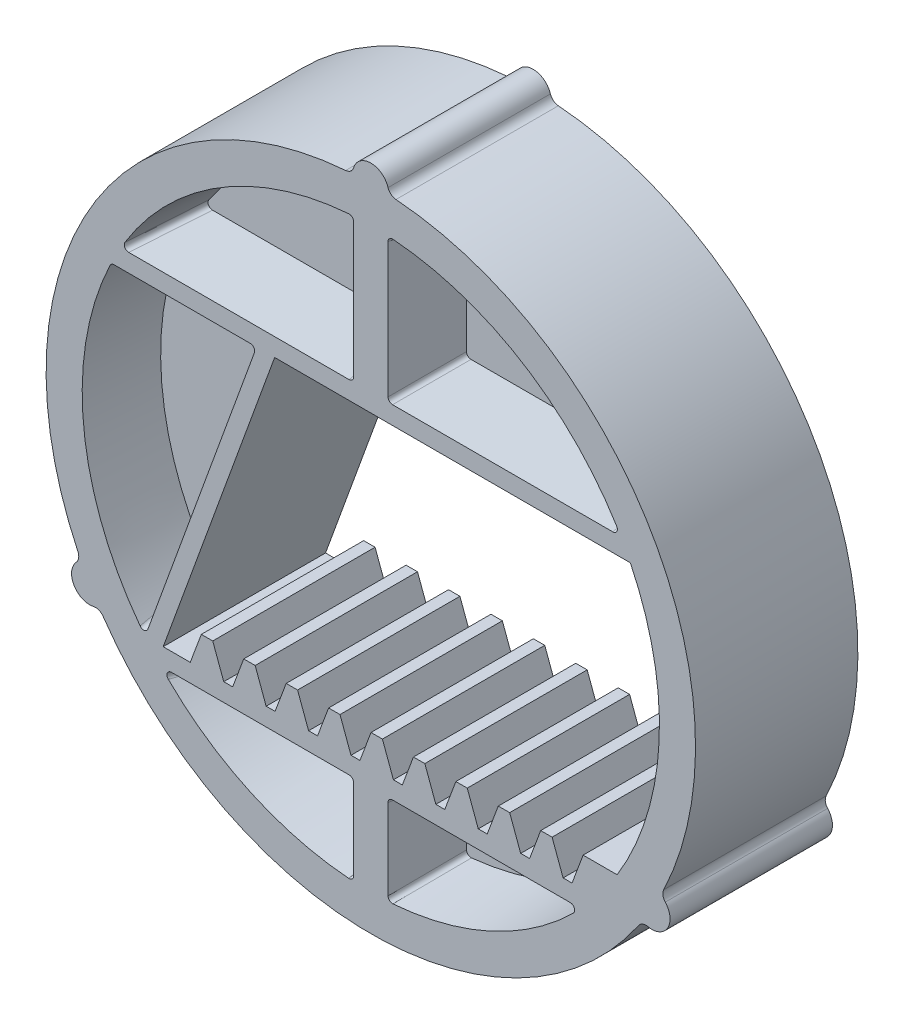
SolidWorks part; units mm, degrees
ref_plane "Plan de face" through (0, 0, 0) normal (0, 0, 1) x (1, 0, 0)
ref_plane "Plan de dessus" through (0, 0, 0) normal (0, 1, 0) x (1, 0, 0)
ref_plane "Plan de droite" through (0, 0, 0) normal (1, 0, 0) x (0, 0, -1)
sketch "Esquisse1" plane through (0, 0, 0) normal (0, 0, 1) x (1, 0, 0)
  line L0 (14.3875, 7) -> (-5.3312, 7)
  line L1 (-5.3312, 7) -> (-11.5097, -9.9753)
  line L2 (-11.5097, -9.9753) -> (-10.0097, -9.9753)
  line L3 (-7.6582, -9.977) -> (-8.1539, -9.977)
  line L4 (-8.1539, -9.977) -> (-8.7634, -8.3253)
  line L5 (-8.7634, -8.3253) -> (-9.3955, -8.3253)
  line L6 (-9.3955, -8.3253) -> (-10.0097, -9.9753)
  line L7 (-5.3067, -9.9787) -> (-5.8023, -9.9787)
  line L8 (-5.8023, -9.9787) -> (-6.4119, -8.327)
  line L9 (-6.4119, -8.327) -> (-7.044, -8.327)
  line L10 (-7.044, -8.327) -> (-7.6582, -9.977)
  line L11 (-2.9552, -9.9805) -> (-3.4508, -9.9805)
  line L12 (-3.4508, -9.9805) -> (-4.0603, -8.3287)
  line L13 (-4.0603, -8.3287) -> (-4.6925, -8.3287)
  line L14 (-4.6925, -8.3287) -> (-5.3067, -9.9787)
  line L15 (-0.6036, -9.9822) -> (-1.0993, -9.9822)
  line L16 (-1.0993, -9.9822) -> (-1.7088, -8.3305)
  line L17 (-1.7088, -8.3305) -> (-2.341, -8.3305)
  line L18 (-2.341, -8.3305) -> (-2.9552, -9.9805)
  line L19 (1.7479, -9.9839) -> (1.2522, -9.9839)
  line L20 (1.2522, -9.9839) -> (0.6427, -8.3322)
  line L21 (0.6427, -8.3322) -> (0.0106, -8.3322)
  line L22 (0.0106, -8.3322) -> (-0.6036, -9.9822)
  line L23 (4.0994, -9.9857) -> (3.6038, -9.9857)
  line L24 (3.6038, -9.9857) -> (2.9942, -8.3339)
  line L25 (2.9942, -8.3339) -> (2.3621, -8.3339)
  line L26 (2.3621, -8.3339) -> (1.7479, -9.9839)
  line L27 (6.451, -9.9874) -> (5.9553, -9.9874)
  line L28 (5.9553, -9.9874) -> (5.3458, -8.3357)
  line L29 (5.3458, -8.3357) -> (4.7136, -8.3357)
  line L30 (4.7136, -8.3357) -> (4.0994, -9.9857)
  line L31 (8.8025, -9.9891) -> (8.3068, -9.9891)
  line L32 (8.3068, -9.9891) -> (7.6973, -8.3374)
  line L33 (7.6973, -8.3374) -> (7.0652, -8.3374)
  line L34 (7.0652, -8.3374) -> (6.451, -9.9874)
  line L35 (11.154, -9.9909) -> (10.6584, -9.9909)
  line L36 (10.6584, -9.9909) -> (10.0488, -8.3391)
  line L37 (10.0488, -8.3391) -> (9.4167, -8.3391)
  line L38 (9.4167, -8.3391) -> (8.8025, -9.9891)
  line L39 (0, -4.95) -> (0, 4.95) construction
  line L41 (13.6539, -8.3409) -> (11.7682, -8.3409)
  line L42 (11.7682, -8.3409) -> (11.154, -9.9909)
  arc A0 (-14.8447, -10.1801) -> (14.8447, -10.1801) centre (0, 0) ccw
  circle A1 centre (0, 0) radius 16
  arc A2 (-16.3226, -8.321) -> (-15.3675, -9.9753) centre (-15.5885, -9) ccw
  arc A3 (-16.3226, -8.321) -> (-16.2386, -7.7658) centre (-16.6897, -7.9815) ccw
  arc A4 (-15.3675, -9.9753) -> (-14.8447, -10.1801) centre (-15.257, -10.4629) cw
  arc A5 (0.9551, 18.2963) -> (-0.9551, 18.2963) centre (0, 18) ccw
  arc A6 (0.9551, 18.2963) -> (1.3939, 17.9459) centre (1.4326, 18.4444) ccw
  arc A7 (-0.9551, 18.2963) -> (-1.3939, 17.9459) centre (-1.4326, 18.4444) cw
  arc A8 (15.3675, -9.9753) -> (14.8447, -10.1801) centre (15.257, -10.4629) ccw
  arc A9 (16.3226, -8.321) -> (16.2386, -7.7658) centre (16.6897, -7.9815) cw
  arc A10 (16.3226, -8.321) -> (15.3675, -9.9753) centre (15.5885, -9) cw
  arc A11 (16.2386, -7.7658) -> (1.3939, 17.9459) centre (0, 0) ccw
  arc A12 (-1.3939, 17.9459) -> (-16.2386, -7.7658) centre (0, 0) ccw
  point P5 (-16.4545, -9.5)
  point P17 (0, 17)
  point P61 (0, 18)
  point P101 (16.4545, -9.5)
  point P102 (-12.5097, -9.9753)
  dimension "D1" = 36
  dimension "D7" = 2
  dimension "D56" = 0.5
  dimension "D58" = 0.5
  dimension "D2" = 1.6517
  dimension "D3" = 0.6321
  dimension "D4" = 1.65
  dimension "D5" = 0.4957
  dimension "D6" = 0.6142
  dimension "D8" = 0.6321
  dimension "D9" = 1.65
  dimension "D10" = 0.4957
  dimension "D11" = 0.6142
  dimension "D12" = 1.6517
  dimension "D13" = 0.6321
  dimension "D14" = 1.65
  dimension "D15" = 0.4957
  dimension "D16" = 0.6142
  dimension "D17" = 1.6517
  dimension "D18" = 0.6321
  dimension "D19" = 1.65
  dimension "D20" = 0.4957
  dimension "D21" = 0.6142
  dimension "D22" = 1.6517
  dimension "D23" = 0.6321
  dimension "D24" = 1.65
  dimension "D25" = 0.4957
  dimension "D26" = 0.6142
  dimension "D27" = 1.6517
  dimension "D28" = 0.6321
  dimension "D29" = 1.65
  dimension "D30" = 0.4957
  dimension "D31" = 0.6142
  dimension "D32" = 1.6517
  dimension "D33" = 0.6321
  dimension "D34" = 1.65
  dimension "D35" = 0.4957
  dimension "D36" = 0.6142
  dimension "D37" = 1.6517
  dimension "D38" = 0.6321
  dimension "D39" = 1.65
  dimension "D40" = 0.4957
  dimension "D41" = 0.6142
  dimension "D42" = 1.6517
  dimension "D43" = 0.6321
  dimension "D44" = 1.65
  dimension "D45" = 0.4957
  dimension "D46" = 0.6142
  dimension "D47" = 1.6517
  dimension "D48" = 11
  dimension "D49" = 1.65
  dimension "D50" = 1.5
  dimension "D51" = 0.6142
  dimension "D52" = 110
  dimension "D53" = 120
  dimension "D54" = 1
  dimension "D55" = 1
  dimension "D57" = 1
extrude "Boss.-Extru.1" add sketch "Esquisse1" along normal blind 9 contours A0 A1 | L0 A1 L41 L42 L35 L36 L37 L38 L31 L32 L33 L34 L27 L28 L29 L30 L23 L24 L25 L26 L19 L20 L21 L22 L15 L16 L17 L18 L11 L12 L13 L14 L7 L8 L9 L10 L3 L4 L5 L6 L2 L1 region at (4.5281, 7.4413, 0) region at (-14.8863, -9.5167, 0)
sketch "Esquisse2" plane through (0, 0, 9) normal (0, 0, 1) x (1, 0, 0)
  line L0 (-6.3312, 7) -> (-14.3875, 7)
  line L1 (-6.3312, 7) -> (-12.5097, -9.9753)
  line L2 (14.3875, 7) -> (-5.3312, 7) construction
  line L3 (-5.3312, 7) -> (-11.5097, -9.9753) construction
  line L4 (-0.9551, 15.9715) -> (-0.9551, 8)
  line L5 (-0.9551, 8) -> (-13.8564, 8)
  line L6 (0.9551, 15.9715) -> (0.9551, 8)
  line L7 (0.9551, 8) -> (13.8564, 8)
  line L8 (-11.6423, -10.9753) -> (-0.9551, -10.9753)
  line L9 (-0.9551, -10.9753) -> (-0.9551, -15.9715)
  line L10 (0.9551, -15.9715) -> (0.9551, -10.9753)
  line L11 (0.9551, -10.9753) -> (11.6423, -10.9753)
  line L12 (-11.5097, -9.9753) -> (-10.0097, -9.9753) construction
  circle A0 centre (0, 0) radius 16 construction
  arc A1 (-14.3875, 7) -> (-12.5097, -9.9753) centre (0, 0) ccw
  arc A2 (-11.6423, -10.9753) -> (-0.9551, -15.9715) centre (0, 0) ccw
  arc A3 (0.9551, -15.9715) -> (11.6423, -10.9753) centre (0, 0) ccw
  arc A4 (-0.9551, 15.9715) -> (-13.8564, 8) centre (0, 0) ccw
  arc A5 (0.9551, 15.9715) -> (13.8564, 8) centre (0, 0) cw
  point P31 (-0.9551, -15.9715)
  dimension "D1" = 0.9397
  dimension "D2" = 1
  dimension "D3" = 1
extrude "Enlèv. mat.-Extru.1" cut sketch "Esquisse2" against normal blind 4 draft 5
fillet "Congé1" radius 0.25 15 edges at (1.1301, -11.1503, 7) (-1.1301, -11.1503, 7) (-6.5811, 6.825, 7) (1.1301, 8.175, 7) (-1.1301, 8.175, 7)
mirror "Symétrie1" about plane through (0, 0, 0) normal (0, 0, 1) rebuild error yes
